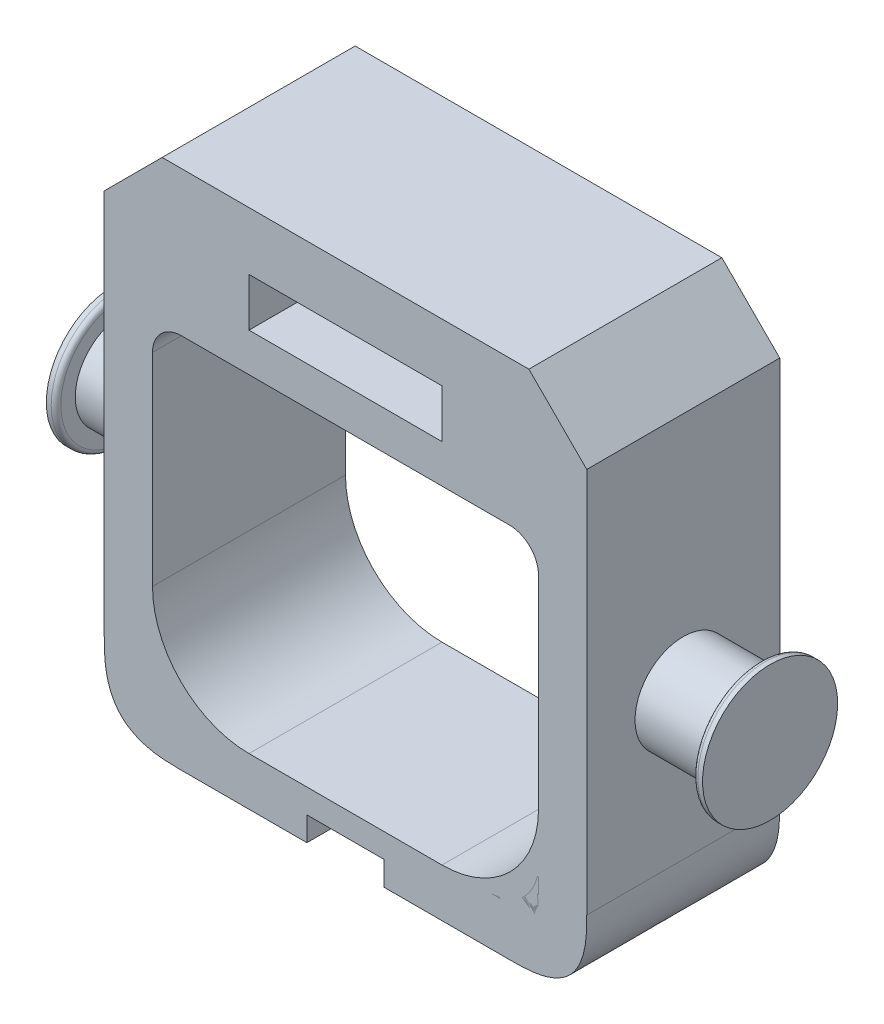
SolidWorks part; units mm, degrees
ref_plane "Front Plane" through (0, 0, 0) normal (0, 0, 1) x (1, 0, 0)
ref_plane "Top Plane" through (0, 0, 0) normal (0, 1, 0) x (1, 0, 0)
ref_plane "Right Plane" through (0, 0, 0) normal (1, 0, 0) x (0, 0, -1)
sketch "Sketch1" plane through (0, 0, 0) normal (0, 0, 1) x (1, 0, 0)
  line L0 (-20, 0) -> (0, 0)
  line L1 (0, 0) -> (0, -17)
  line L2 (0, -17) -> (-20, -17)
  line L3 (-20, -17) -> (-20, 0)
  line L4 (-22.5, 7.5) -> (-22.5, -19.5)
  line L5 (-22.5, -19.5) -> (2.5, -19.5)
  line L6 (2.5, -19.5) -> (2.5, 7.5)
  line L7 (-22.5, 7.5) -> (2.5, 7.5)
  dimension "D1" = 20
  dimension "D2" = 17
  dimension "D3" = 7.5
  dimension "D4" = 27
  dimension "D5" = 25
  dimension "D6" = 2.5
extrude "Boss-Extrude1" add sketch "Sketch1" along normal blind 10
fillet "Fillet1" radius 4 2 edges at (-22.5, -19.5, 5) (2.5, -19.5, 5) curvature continuous yes
ref_plane "Plane1" through (-20, -17, 10) normal (0, -1, 0) x (-1, 0, 0)
sketch "Sketch3" plane through (0, 0, 10) normal (0, 0, 1) x (1, 0, 0)
  line L1 (0, 0) -> (-10, -17)
  line L2 (-21.65, -17) -> (-18.35, -17) construction
  line L3 (-20, 0) -> (-20, -1.5)
  line L4 (-20, 0) -> (-20, -17) construction
  line L5 (-20, 0) -> (-18.5, 0)
  arc A0 (-20, -1.5) -> (-18.5, 0) centre (-18.5, -1.5) cw
  line M13 (-20, -17) -> (-20, 0)
  line M14 (-20, 0) -> (0, 0)
extrude "Boss-Extrude2" add sketch "Sketch3" against normal blind 10 contours A0 M13 M14 region at (-19.6649, -0.3351, 10)
sketch "Sketch4" plane through (0, 0, 10) normal (0, 0, 1) x (1, 0, 0)
  line L0 (0, 0) -> (0, -1.4954)
  line L1 (0, -17) -> (0, 0) construction
  line L2 (0, 0) -> (-1.4954, 0)
  line L3 (0, 0) -> (-18.5, 0) construction
  arc A0 (0, -1.4954) -> (-1.4954, 0) centre (-1.4954, -1.4954) ccw
extrude "Boss-Extrude3" add sketch "Sketch4" against normal blind 10
sketch "Sketch6" plane through (0, 0, 10) normal (0, 0, 1) x (1, 0, 0)
  line L0 (0, -17) -> (0, -14.5)
  line L1 (0, -17) -> (0, -1.4954) construction
  line L2 (0, -17) -> (-2.5, -17)
  line L3 (-20, -17) -> (0, -17) construction
  arc A0 (-2.5, -17) -> (0, -14.5) centre (-2.5, -14.5) ccw
extrude "Boss-Extrude4" add sketch "Sketch6" against normal blind 7.5 separate body
sketch "Sketch7" plane through (0, 0, 10) normal (0, 0, 1) x (1, 0, 0)
  line L0 (-20, -17) -> (-15, -17)
  line L1 (-21.65, -17) -> (-18.35, -17) construction
  line L2 (-20, -1.5) -> (-20, -17) construction
  line L3 (-20, -17) -> (-20, -12)
  line L4 (0, -17) -> (-5, -17)
  line L5 (-20, -17) -> (0, -17) construction
  line L6 (0, -17) -> (0, -12)
  line L7 (0, -17) -> (0, -1.4954) construction
  arc A0 (-15, -17) -> (-20, -12) centre (-15, -12) cw
  arc A1 (-5, -17) -> (0, -12) centre (-5, -12) ccw
extrude "Boss-Extrude5" add sketch "Sketch7" against normal blind 10
chamfer "Chamfer1" distance 3 angle 45 2 edges at (2.5, 7.5, 5) (-22.5, 7.5, 5)
sketch "Sketch8" plane through (0, 0, 10) normal (0, 0, 1) x (1, 0, 0)
  line L0 (-15, 4.5) -> (-5, 4.5)
  line L1 (-5, 4.5) -> (-5, 2)
  line L2 (-5, 2) -> (-15, 2)
  line L3 (-15, 2) -> (-15, 4.5)
  line L4 (-0.5, 7.5) -> (-19.5, 7.5) construction
  line L8 (-22.5, 4.5) -> (-22.5, -15.5) construction
  dimension "D1" = 7.5
  dimension "D2" = 3
  dimension "D3" = 2.5
extrude "Cut-Extrude1" cut sketch "Sketch8" against normal blind 10.5 contours L3 L2 L1 L0 region at (-10, 3.25, 10)
sketch "Sketch9" plane through (0, 0, 10) normal (0, 0, 1) x (1, 0, 0)
  line L0 (-18.5, -19.5) -> (-1.5, -19.5) construction
  line L1 (-6.1419, -18.5) -> (-4.1419, -18.5)
  line L2 (-6.1419, -18.5) -> (-6.1419, -19.5)
  line L3 (-6.1419, -19.5) -> (-4.1419, -19.5)
  line L4 (-4.1419, -18.5) -> (-4.1419, -19.5)
  dimension "D1" = 1
sketch "Sketch12" plane through (0, 0, 0) normal (0, 0, -1) x (-1, 0, 0)
  line L10 (19.5, 7.5) -> (0.5, 7.5)
  line L11 (0.5, 7.5) -> (-2.5, 4.5)
  line L12 (-2.5, 4.5) -> (-2.5, -15.5)
  line L13 (1.5, -19.5) -> (18.5, -19.5)
  line L14 (22.5, -15.5) -> (22.5, 4.5)
  line L15 (22.5, 4.5) -> (19.5, 7.5)
  line L18 (-2.5, 4.5) -> (-2.5, -15.5)
  spline S2 degree 2 poles (67.845, 982.0209) (-3.6492, 1.7622) (-2.4812, -16.3302) (-2.4524, -16.7775) (-2.3691, -17.1519) (-2.1636, -18.0767) (-1.6244, -18.6183) (-1.0848, -19.1602) (-0.1577, -19.3678) (0.2161, -19.4515) (0.6646, -19.4809) (18.738, -20.6634) (998.9799, 51.3297) knots -7.651516 -7.651516 -7.651516 0.125 0.125 0.25 0.25 0.5 0.5 0.75 0.75 0.875 0.875 8.610168 8.610168 8.610168 only from (-2.5, -15.5) to (1.5, -19.5)
  spline S3 degree 2 poles (-979.0209, 50.845) (1.2378, -20.6492) (19.3302, -19.4812) (19.7775, -19.4524) (20.1519, -19.3691) (21.0767, -19.1636) (21.6183, -18.6244) (22.1602, -18.0848) (22.3678, -17.1577) (22.4515, -16.7839) (22.4809, -16.3354) (23.6634, 1.738) (-48.3297, 981.9799) knots -7.651516 -7.651516 -7.651516 0.125 0.125 0.25 0.25 0.5 0.5 0.75 0.75 0.875 0.875 8.610168 8.610168 8.610168 only from (18.5, -19.5) to (22.5, -15.5)
  dimension "D1" = 0
ref_plane "Plane2" through (-10, 0, 0) normal (-1, 0, 0) x (0, 0, 1)
sketch "Sketch19" plane through (0, 0, 10) normal (0, 0, 1) x (1, 0, 0)
  line L0 (-18.5, -19.5) -> (-1.5, -19.5) construction
  line L1 (-12, -18.25) -> (-8, -18.25)
  line L2 (-12, -18.25) -> (-12, -19.5)
  line L3 (-12, -19.5) -> (-8, -19.5)
  line L4 (-8, -18.25) -> (-8, -19.5)
  line L5 (-22.5, 4.5) -> (-22.5, -15.5) construction
  dimension "D1" = 10.5
  dimension "D2" = 4
extrude "Cut-Extrude5" cut sketch "Sketch19" against normal through all
sketch "Sketch20" plane through (2.5, 0, 0) normal (1, 0, 0) x (0, 0, -1)
  circle A0 centre (-5, -8) radius 2.5
extrude "Boss-Extrude10" add sketch "Sketch20" along normal blind 4.5
sketch "Sketch21" plane through (7, 0, 0) normal (1, 0, 0) x (0, 0, -1)
  circle A0 centre (-5, -8) radius 3.5
extrude "Boss-Extrude11" add sketch "Sketch21" against normal blind 0.5
fillet "Fillet2" radius 0.25 1 edges at (6.5, -8, 1.5)
mirror "Mirror1" about plane through (-10, 0, 0) normal (-1, 0, 0) of "Boss-Extrude11", "Boss-Extrude10"
fillet "Fillet3" radius 0.25 1 edges at (-26.5, -8, 1.5)
